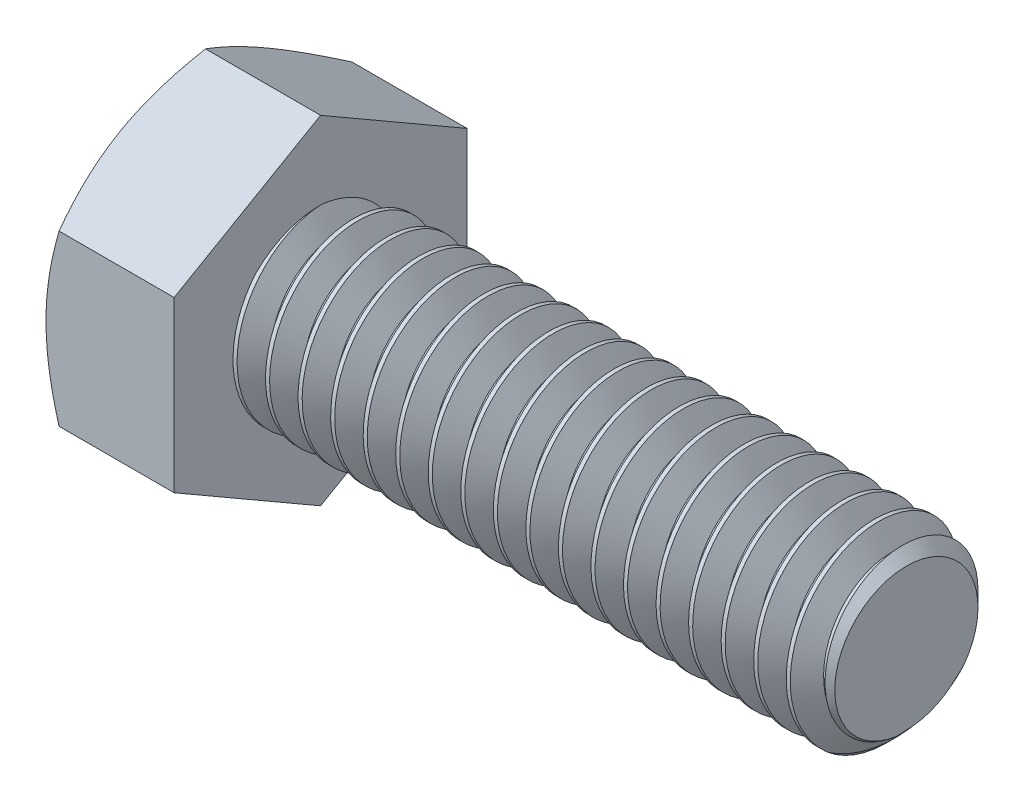
SolidWorks part; units mm, degrees
ref_plane "Front Plane" through (0, 0, 0) normal (0, 0, 1) x (1, 0, 0)
ref_plane "Top Plane" through (0, 0, 0) normal (0, 1, 0) x (1, 0, 0)
ref_plane "Right Plane" through (0, 0, 0) normal (1, 0, 0) x (0, 0, -1)
sketch "Sketch1" plane through (0, 0, 0) normal (0, 0, 1) x (1, 0, 0)
  line L0 (-15.4781, 0) -> (15.4781, 0) construction
  line L1 (15.4781, 3.9688) -> (15.4781, -3.9688) construction
  line L2 (-9.9219, 6.35) -> (-9.9219, -6.35) construction
  line L3 (-15.4781, 6.35) -> (-15.4781, -6.35) construction
  point P9 (-9.9219, 0)
  point P10 (10.5392, -3.9688)
  dimension "D1" = 4.9389
  dimension "Screw Dia" = 7.9375
  dimension "Hex" = 12.7
  dimension "Head Ht" = 5.5562
  dimension "Screw Lenght" = 25.4
ref_plane "Plane2" through (15.4781, 0, 0) normal (1, 0, 0) x (0, 0, -1)
sketch "Sketch5" plane through (15.4781, 0, 0) normal (1, 0, 0) x (0, 0, -1)
  circle A0 centre (0, 0) radius 3.9688
extrude "Boss-Extrude3" add sketch "Sketch5" against normal up to vertex (25.4 mm away) up to point (-9.9219, 0, 0)
sketch "Sketch9" plane through (15.4781, 0, 0) normal (1, 0, 0) x (0, 0, -1)
  circle A1 centre (0, 0) radius 3.9688
  circle A2 centre (0, 0) radius 3.9688
  dimension "D1" = 0
curve "Helix/Spiral1" pitch 1.4111 height 26.8111 turns 19 parameters "Pitch"=1.4111
chamfer "Chamfer1" distance 0.8636 angle 45 1 edges at (15.4781, 0, -3.9688)
sketch "Sketch10" plane through (0, 0, 0) normal (0, 0, 1) x (1, 0, 0)
  line L0 (15.4781, 3.9688) -> (16.0073, 3.0522)
  line L1 (16.0073, 3.0522) -> (16.1837, 3.0522)
  line L2 (16.1837, 3.0522) -> (16.7128, 3.9687)
  line L3 (15.4781, 3.9688) -> (16.7128, 3.9687)
  line L4 (16.0955, 3.9688) -> (16.0955, 3.0522) construction
  line L5 (15.7427, 3.5105) -> (16.4483, 3.5105) construction
  dimension "D1" = 60
  dimension "D2" = 0.1764
  dimension "D3" = 0.7056
sweep "Cut-Sweep1" cut profiles "Sketch10" path "Helix/Spiral1"
sketch "Sketch6" plane through (-9.9219, 0, 0) normal (-1, 0, 0) x (0, 0, 1)
  line L0 (0, 6.35) -> (0, -6.35) construction
  line L1 (6.35, 3.6662) -> (0, 7.3323)
  line L2 (0, 7.3323) -> (-6.35, 3.6662)
  line L3 (-6.35, 3.6662) -> (-6.35, -3.6662)
  line L4 (-6.35, -3.6662) -> (0, -7.3323)
  line L5 (0, -7.3323) -> (6.35, -3.6662)
  line L6 (6.35, -3.6662) -> (6.35, 3.6662)
  circle A0 centre (0, 0) radius 6.35 construction
extrude "Boss-Extrude4" add sketch "Sketch6" along normal up to vertex (5.5563 mm away) up to point (-15.4781, -6.35, 0)
sketch "Sketch7" plane through (-15.4781, 0, 0) normal (-1, 0, 0) x (0, 0, 1)
  circle A0 centre (0, 0) radius 6.35 construction
  circle A1 centre (0, 0) radius 6.35
sketch "Sketch8" plane through (-15.4781, 0, 0) normal (-1, 0, 0) x (0, 0, 1)
  circle A0 centre (0, 0) radius 6.35 construction
  circle A1 centre (0, 0) radius 6.35
extrude "Cut-Extrude3" cut sketch "Sketch8" against normal through all draft 60 flip side to cut
sketch "Sketch12" plane through (-15.4781, 0, 0) normal (-1, 0, 0) x (0, 0, 1)
  line L0 (0, 4.8895) -> (0, 2.7305) construction
  line L1 (0.1905, 4.8895) -> (0.1905, 2.7305)
  line L2 (-0.1905, 4.8895) -> (-0.1905, 2.7305)
  line L3 (0, 3.9688) -> (0, -3.9688) construction
  arc A0 (0.1905, 4.8895) -> (-0.1905, 4.8895) centre (0, 4.8895) ccw
  arc A1 (-0.1905, 2.7305) -> (0.1905, 2.7305) centre (0, 2.7305) ccw
  circle A3 centre (0, 0) radius 2.54 construction
  circle A4 centre (0, 0) radius 5.08 construction
  point P2 (0, 3.81)
  dimension "D1" = 5.08
  dimension "D3" = 10.16
  dimension "D2" = 0.381
extrude "Cut-Extrude4" cut sketch "Sketch12" against normal blind 0.254
pattern_circular "CirPattern1" count 3 over 360 about axis through (0, 0, 0) along (1, 0, 0) of "Cut-Extrude4"
equation "\"D2@Sketch10\" = \"Pitch@Helix/Spiral1\"*.125"
equation "\"D3@Sketch10\" = \"Pitch@Helix/Spiral1\"*.5"
equation "\"D1@Chamfer1\" = \"Pitch@Helix/Spiral1\"*.612"
equation "\"D1@Sketch12\" = \"Hex@Sketch1\"*.4"
equation "\"D3@Sketch12\" = \"Hex@Sketch1\"*.8"
equation "\"D2@Sketch12\" = \"Hex@Sketch1\"*.03"
equation "\"D1@Sketch1\" = \"Pitch@Helix/Spiral1\"*3.5"
equation "\"D3@Helix/Spiral1\" = \"Screw Lenght@Sketch1\"+\"Pitch@Helix/Spiral1\""
